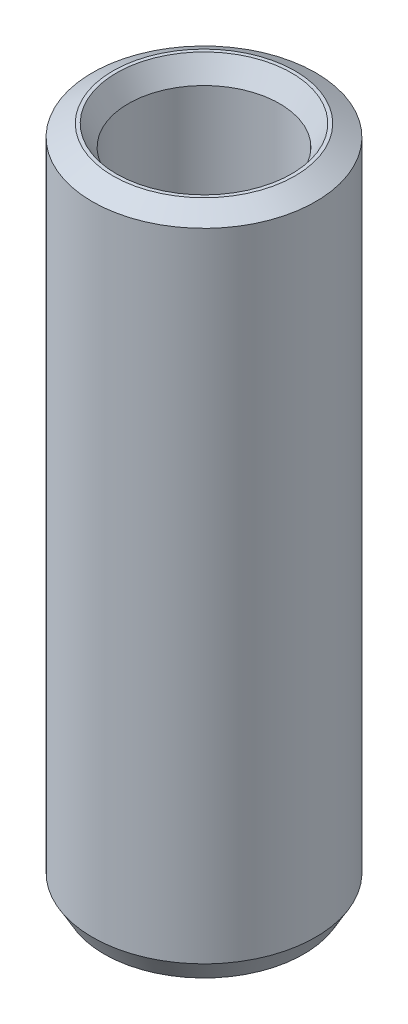
SolidWorks part; units mm, degrees
ref_plane "Front Plane" through (0, 0, 0) normal (0, 0, 1) x (1, 0, 0)
ref_plane "Top Plane" through (0, 0, 0) normal (0, 1, 0) x (1, 0, 0)
ref_plane "Right Plane" through (0, 0, 0) normal (1, 0, 0) x (0, 0, -1)
sketch "Sketch1" plane through (0, 0, 0) normal (0, 1, 0) x (1, 0, 0)
  circle A0 centre (0, 0) radius 35
  dimension "SLEEVE_OD" = 70
extrude "Boss-Extrude1" add sketch "Sketch1" along normal blind 209.8201
sketch "Sketch2" plane through (0, 0, 0) normal (0, 1, 0) x (1, 0, 0)
  circle A0 centre (0, 0) radius 23.7015
  dimension "BORE_D" = 47.403
extrude "Cut-Extrude1" cut sketch "Sketch2" along normal through all
chamfer "Chamfer1" distance 3.7348 angle 60 4 edges at (0, 209.8201, 23.7015) (0, 0, 23.7015) (0, 0, 35) (0, 209.8201, 35) first distance on face at (0, 209.8201, 23.7015) first distance on face at (0, 0, 23.7015) first distance on face at (0, 209.8201, 35)
